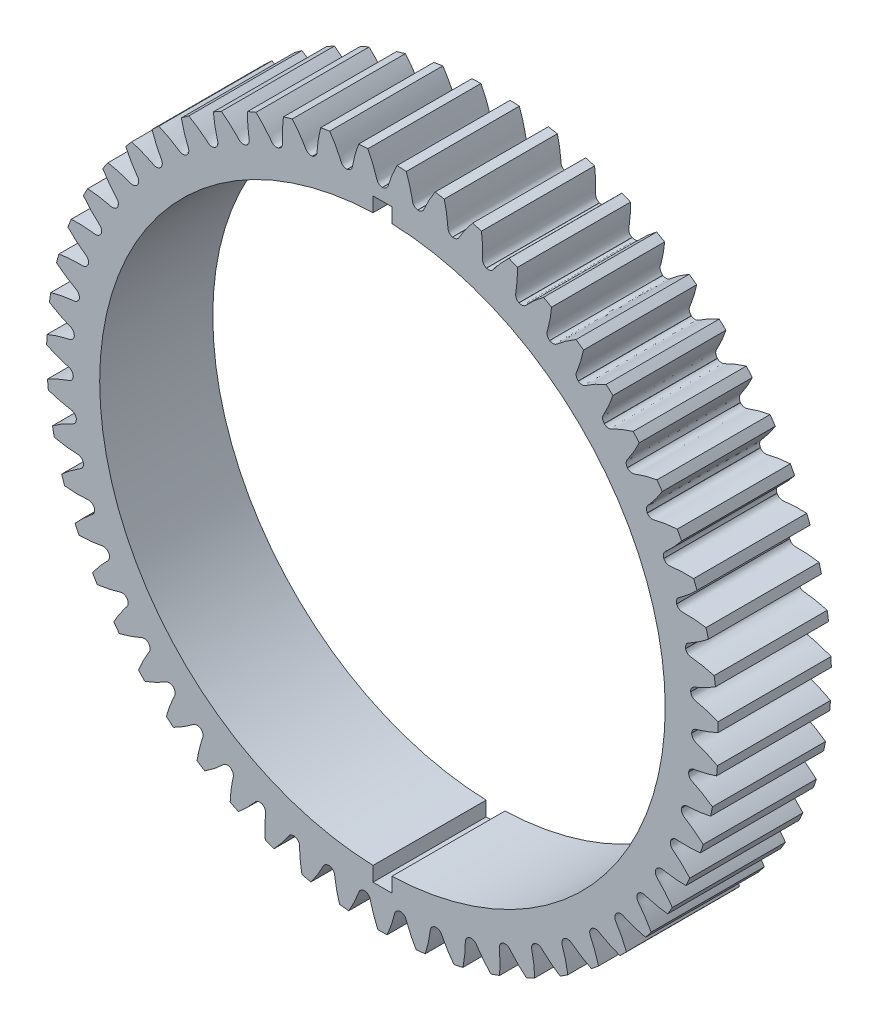
SolidWorks part; units mm, degrees
ref_plane "前视基准面" through (0, 0, 0) normal (0, 0, 1) x (1, 0, 0)
ref_plane "上视基准面" through (0, 0, 0) normal (0, 1, 0) x (1, 0, 0)
ref_plane "右视基准面" through (0, 0, 0) normal (1, 0, 0) x (0, 0, -1)
sketch "草图1" plane through (0, 0, 0) normal (0, 0, 1) x (1, 0, 0)
  circle A0 centre (0, 0) radius 35.625
extrude "凸台-拉伸1" add sketch "草图1" along normal blind 12
ref_axis "基准轴1" through (0, 0, -0.6) along (0, 0, 1)
sketch "草图2" plane through (0, 0, 0) normal (0, 0, 1) x (1, 0, 0)
  line L0 (0, 0) -> (0, 35.625) construction
  circle A0 centre (0, 0) radius 35.625 construction
  arc A1 (0.01, 32.8125) -> (-0.01, 32.8125) centre (0, 0) ccw
  arc A2 (5.0776, 40.3309) -> (-5.0776, 40.3309) centre (0, 0) ccw
  spline S0 degree 3 poles (0.01, 32.8125) (0.5386, 32.8846) (0.614, 33.2997) (0.7615, 33.7567) (0.8267, 33.9488) (0.9003, 34.1516) (0.9825, 34.365) (1.0739, 34.5887) (1.1748, 34.8223) (1.2858, 35.0656) (1.4072, 35.3183) (1.5395, 35.5801) (1.683, 35.8506) (1.8381, 36.1295) (2.0054, 36.4163) (2.185, 36.7108) (2.3775, 37.0125) (2.5831, 37.3211) (2.8022, 37.6361) (3.0352, 37.9572) (3.2824, 38.2838) (3.544, 38.6155) (3.8204, 38.952) (4.1119, 39.2926) (4.5267, 39.7583) (4.8528, 40.1026) (5.0776, 40.3309) knots 0 0 0 0 0.114374 0.135076 0.157187 0.180707 0.205635 0.231972 0.259717 0.288871 0.319433 0.351404 0.384784 0.419572 0.455769 0.493374 0.532388 0.572811 0.614642 0.657882 0.70253 0.748587 0.796052 0.844926 0.895209 1 1 1 1
  spline S1 degree 3 poles (-0.01, 32.8125) (-0.5386, 32.8846) (-0.614, 33.2997) (-0.7615, 33.7567) (-0.8267, 33.9488) (-0.9003, 34.1516) (-0.9825, 34.365) (-1.0739, 34.5887) (-1.1748, 34.8223) (-1.2858, 35.0656) (-1.4072, 35.3183) (-1.5395, 35.5801) (-1.683, 35.8506) (-1.8381, 36.1295) (-2.0054, 36.4163) (-2.185, 36.7108) (-2.3775, 37.0125) (-2.5831, 37.3211) (-2.8022, 37.6361) (-3.0352, 37.9572) (-3.2824, 38.2838) (-3.544, 38.6155) (-3.8204, 38.952) (-4.1119, 39.2926) (-4.5267, 39.7583) (-4.8528, 40.1026) (-5.0776, 40.3309) knots 0 0 0 0 0.114374 0.135076 0.157187 0.180707 0.205635 0.231972 0.259717 0.288871 0.319433 0.351404 0.384784 0.419572 0.455769 0.493374 0.532388 0.572811 0.614642 0.657882 0.70253 0.748587 0.796052 0.844926 0.895209 1 1 1 1
extrude "切除-拉伸1" cut sketch "草图2" along normal through all
pattern_circular "阵列(圆周)1" count 55 every 6.545 about axis through (0, 0, -0.6) along (0, 0, 1) of "切除-拉伸1"
sketch "草图3" plane through (0, 0, 0) normal (0, 0, 1) x (1, 0, 0)
  circle A0 centre (0, 0) radius 34.375 construction
  dimension "Dn" = 68.75
sketch "草图4" plane through (0, 0, 12) normal (0, 0, 1) x (1, 0, 0)
  circle A0 centre (0, 0) radius 30
  dimension "D1" = 60
extrude "切除-拉伸2" cut sketch "草图4" against normal through all
sketch "草图5" plane through (0, 0, 12) normal (0, 0, 1) x (1, 0, 0)
  line L1 (-1, -31.5292) -> (1, -31.5292)
  line L2 (-1, -31.5292) -> (-1, 31.5292)
  line L3 (-1, 31.5292) -> (1, 31.5292)
  line L4 (1, -31.5292) -> (1, 31.5292)
  line L5 (-1, -31.5292) -> (1, 31.5292) construction
  line L6 (-1, 31.5292) -> (1, -31.5292) construction
  point P0 (0, 0)
  dimension "D1" = 2
extrude "切除-拉伸3" cut sketch "草图5" against normal through all
